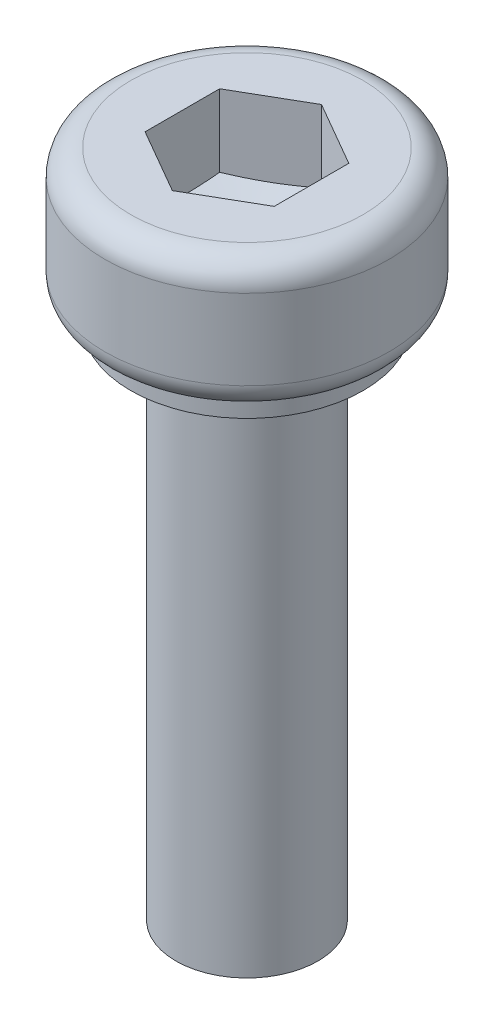
SolidWorks part; units mm, degrees
ref_plane "Front Plane" through (0, 0, 0) normal (0, 0, 1) x (1, 0, 0)
ref_plane "Top Plane" through (0, 0, 0) normal (0, 1, 0) x (1, 0, 0)
ref_plane "Right Plane" through (0, 0, 0) normal (1, 0, 0) x (0, 0, -1)
sketch "Sketch1" plane through (0, 0, 0) normal (0, 0, 1) x (1, 0, 0)
  line L0 (0, 4.0942) -> (0, -5.2249) construction
  line L1 (0, 6.475) -> (2.25, 6.475)
  line L2 (2.75, 5.975) -> (2.75, 4.425)
  line L3 (2.25, 3.525) -> (1.375, 3.525)
  line L4 (1.375, 3.525) -> (1.375, -6.475)
  line L5 (1.375, -6.475) -> (0, -6.475)
  line L6 (0, -6.475) -> (0, 6.475)
  line L7 (2.25, 3.525) -> (2.25, 3.925)
  line L8 (2.75, 3.525) -> (2.25, 3.525) construction
  line L9 (2.75, 4.425) -> (2.75, 3.525) construction
  line L10 (2.75, 6.475) -> (2.75, 5.975) construction
  line L11 (2.25, 6.475) -> (2.75, 6.475) construction
  arc A0 (2.25, 3.925) -> (2.75, 4.425) centre (2.25, 4.425) ccw
  arc A1 (2.25, 6.475) -> (2.75, 5.975) centre (2.25, 5.975) cw
  point P5 (0, 0)
  point P17 (0, 0)
  point P18 (0, 0)
  point P19 (2.25, 2.4541)
  dimension "D5" = 0.5
  dimension "D1" = 10
  dimension "D2" = 1.375
  dimension "D3" = 2.95
  dimension "D4" = 2.75
  dimension "D6" = 0.4
revolve "Revolve1" add sketch "Sketch1" angle 360 about L0
sketch "Sketch2" plane through (0, 6.475, 0) normal (0, 1, 0) x (1, 0, 0)
  line L1 (0, 1.4434) -> (-1.25, 0.7217)
  line L2 (-1.25, 0.7217) -> (-1.25, -0.7217)
  line L3 (-1.25, -0.7217) -> (0, -1.4434)
  line L4 (0, -1.4434) -> (1.25, -0.7217)
  line L5 (1.25, -0.7217) -> (1.25, 0.7217)
  line L6 (1.25, 0.7217) -> (0, 1.4434)
  circle A0 centre (0, 0) radius 1.25 construction
  dimension "D1" = 2.5
extrude "Boss-Extrude1" add sketch "Sketch2" against normal blind 2 separate body
sketch "Sketch3" plane through (0, 0, 0) normal (1, 0, 0) x (0, 0, -1)
  line L0 (0, 4.875) -> (0.4, 4.875)
  line L1 (0.4, 4.875) -> (1.4434, 5.075)
  line L2 (1.4434, 4.475) -> (1.4434, 6.475) construction
  line L3 (1.4434, 5.075) -> (1.4434, 4.475)
  line L4 (1.4434, 4.475) -> (0, 4.475)
  line L5 (-0.7217, 4.475) -> (0.7217, 4.475) construction
  line L6 (0, 4.475) -> (0, 4.875)
  line L7 (-0.7217, 6.475) -> (0.7217, 6.475) construction
  dimension "D1" = 1.6
  dimension "D2" = 1.4
  dimension "D3" = 0.4
revolve "Cut-Revolve1" cut sketch "Sketch3" angle 360 about L6
combine bodies "Combine1" operation type subtract main body 101 bodies to subtract 104
equation "\"Length\"= 10mm"
equation "\"D1@Sketch1\"=\"Length\""
equation "\"ThreadDiam\"= 2.75"
equation "\"D2@Sketch1\"=\"ThreadDiam\"/2"
equation "\"HeadHeight\"=2.95"
equation "\"D3@Sketch1\"=\"HeadHeight\""
equation "\"HeadDiam\"= 5.5"
equation "\"D4@Sketch1\"=\"HeadDiam\"/2"
equation "\"HexSize\"=2.5"
equation "\"D1@Sketch2\"=\"HexSize\""
